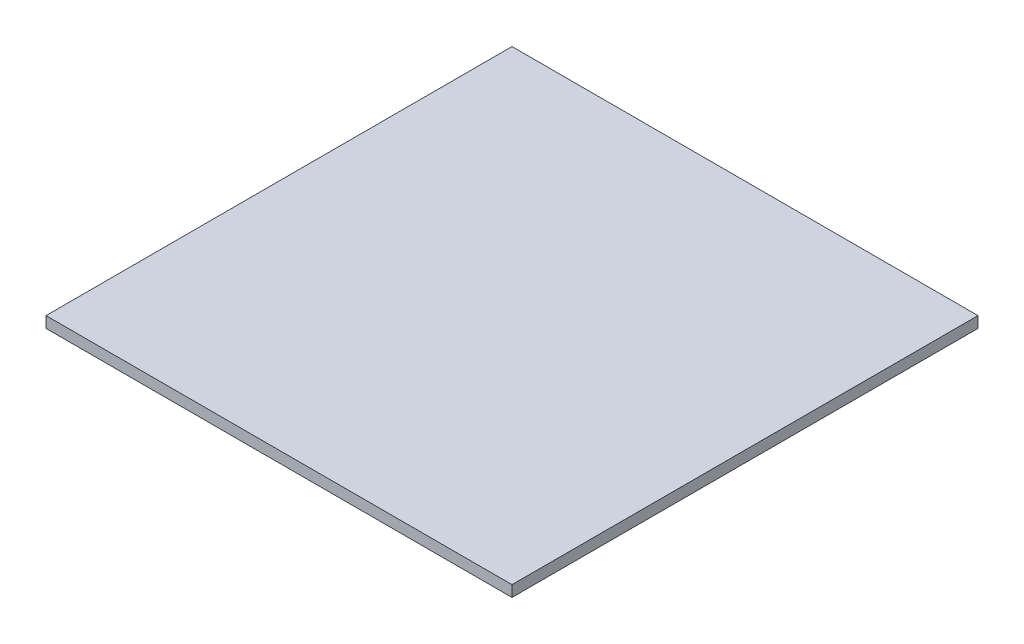
SolidWorks part; units mm, degrees
ref_plane "Front Plane" through (0, 0, 0) normal (0, 0, 1) x (1, 0, 0)
ref_plane "Top Plane" through (0, 0, 0) normal (0, 1, 0) x (1, 0, 0)
ref_plane "Right Plane" through (0, 0, 0) normal (1, 0, 0) x (0, 0, -1)
sketch "Sketch1" plane through (0, 0, 0) normal (0, 1, 0) x (1, 0, 0)
  line L1 (200, 200) -> (-200, 200)
  line L2 (200, 200) -> (200, -200)
  line L3 (200, -200) -> (-200, -200)
  line L4 (-200, 200) -> (-200, -200)
  line L5 (200, 200) -> (-200, -200) construction
  line L6 (200, -200) -> (-200, 200) construction
  point P0 (0, 0)
  dimension "D1" = 400
  dimension "D2" = 400
extrude "Boss-Extrude1" add sketch "Sketch1" along normal blind 9.525
